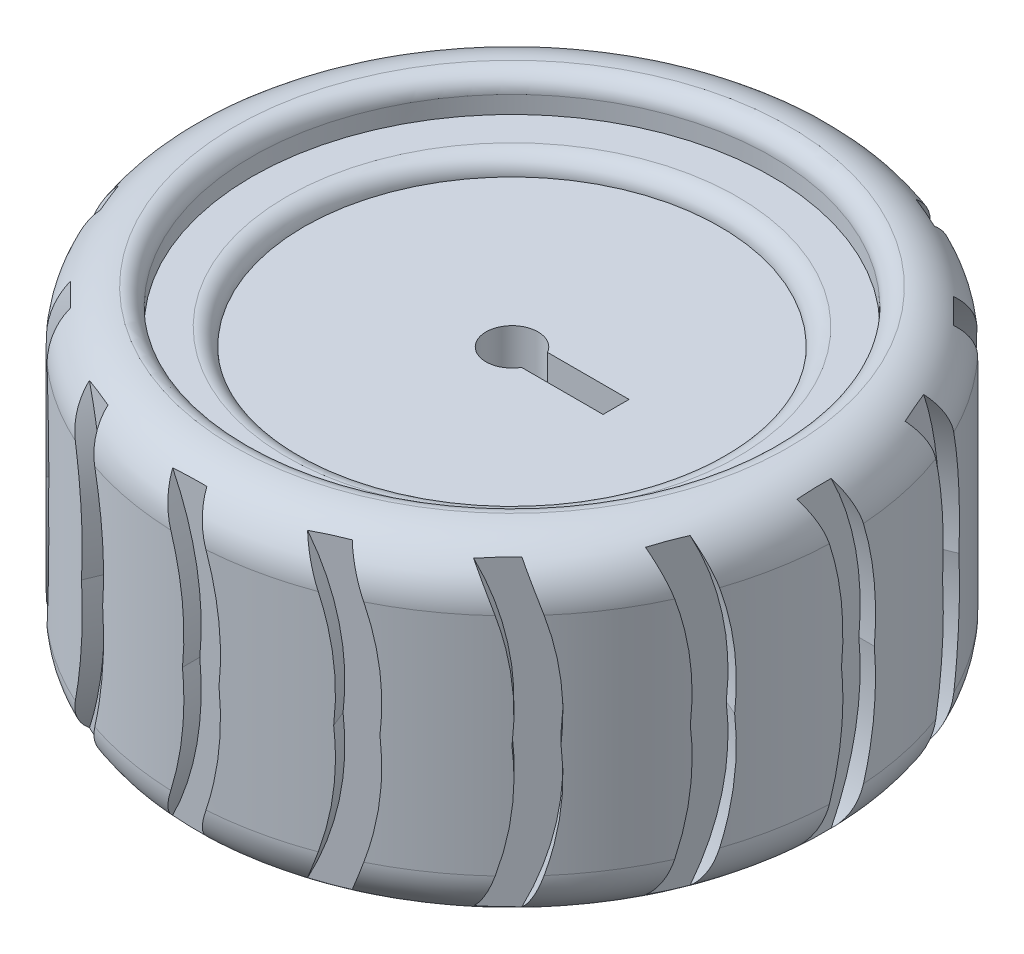
SolidWorks part; units mm, degrees
ref_plane "Front Plane" through (0, 0, 0) normal (0, 0, 1) x (1, 0, 0)
ref_plane "Top Plane" through (0, 0, 0) normal (0, 1, 0) x (1, 0, 0)
ref_plane "Right Plane" through (0, 0, 0) normal (1, 0, 0) x (0, 0, -1)
sketch "草图1" plane through (0, 0, 0) normal (0, 0, 1) x (1, 0, 0)
  line L0 (-688.0523, 0) -> (33714.563, 0) construction
  line L1 (0, -688.0523) -> (0, -10) construction
  line L3 (13, -7.5) -> (15, -7.5)
  line L4 (15, -7.5) -> (15, 7.5)
  line L5 (15, 7.5) -> (12, 7.5)
  line L6 (13, -7.5) -> (13, -2.5)
  line L7 (13, -2.5) -> (12, -2.5)
  line L8 (0, 6.5) -> (12, 6.5)
  line L9 (12, 6.5) -> (12, 7.5)
  line L10 (0, -2.5) -> (0, 33714.563) construction
  line L11 (0, 6.5) -> (0, -2.5)
  arc A0 (12, -2.5) -> (0, -2.5) centre (6, 5.8164) cw
  point P4 (15, 0)
  dimension "D1" = 15
  dimension "D3" = 2
  dimension "D4" = 5
  dimension "D6" = 1
revolve "旋转1" add sketch "草图1" angle 360 about L10
sketch "草图2" plane through (0, 6.5, 0) normal (0, 1, 0) x (1, 0, 0)
  line L0 (-1000, 0) -> (49000, 0) construction
  line L2 (1.299, -0.75) -> (6, -0.75)
  line L4 (1.299, 0.75) -> (6, 0.75)
  line L5 (6, -0.75) -> (6, 0.75)
  arc A0 (1.299, 0.75) -> (1.299, -0.75) centre (0, 0) ccw
  dimension "D1" = 3
  dimension "D2" = 1.5
extrude "切除-拉伸1" cut sketch "草图2" against normal through all both and the other way through all
sketch "草图3" plane through (0, -7.5, 0) normal (0, -1, 0) x (1, 0, 0)
  line L0 (12.9783, -0.75) -> (14.9812, -0.75)
  line L5 (12.7807, -2.3777) -> (14.7254, -2.857)
  line L6 (12.4217, -3.8341) -> (14.3664, -4.3135)
  line L7 (11.8403, -5.3672) -> (13.6138, -6.298)
  line L8 (11.1432, -6.6954) -> (12.9167, -7.6262)
  line L9 (12.9783, 0.75) -> (14.9812, 0.75)
  line L10 (10.2118, -8.0449) -> (11.711, -9.373)
  line L11 (9.2171, -9.1676) -> (10.7163, -10.4958)
  line L12 (7.9898, -10.2549) -> (9.1276, -11.9033)
  line L13 (6.7553, -11.107) -> (7.8931, -12.7554)
  line L14 (5.3034, -11.869) -> (6.0137, -13.7417)
  line L15 (3.9009, -12.4009) -> (4.6112, -14.2737)
  line L16 (2.3089, -12.7933) -> (2.5503, -14.7816)
  line L17 (0.8198, -12.9741) -> (1.0613, -14.9624)
  line L18 (-0.8198, -12.9741) -> (-1.0613, -14.9624)
  line L19 (-2.3089, -12.7933) -> (-2.5503, -14.7816)
  line L20 (-3.9009, -12.4009) -> (-4.6112, -14.2737)
  line L21 (-5.3034, -11.869) -> (-6.0137, -13.7417)
  line L22 (-6.7553, -11.107) -> (-7.8931, -12.7554)
  line L23 (-7.9898, -10.2549) -> (-9.1276, -11.9033)
  line L24 (-9.2171, -9.1676) -> (-10.7163, -10.4958)
  line L25 (-10.2118, -8.0449) -> (-11.711, -9.373)
  line L26 (-11.1432, -6.6954) -> (-12.9167, -7.6262)
  line L27 (-11.8403, -5.3672) -> (-13.6138, -6.298)
  line L28 (-12.4217, -3.8341) -> (-14.3664, -4.3135)
  line L29 (-12.7807, -2.3777) -> (-14.7254, -2.857)
  line L30 (-12.9783, -0.75) -> (-14.9812, -0.75)
  line L31 (-12.9783, 0.75) -> (-14.9812, 0.75)
  line L32 (-12.7807, 2.3777) -> (-14.7254, 2.857)
  line L33 (-12.4217, 3.8341) -> (-14.3664, 4.3135)
  line L34 (-11.8403, 5.3672) -> (-13.6138, 6.298)
  line L35 (-11.1432, 6.6954) -> (-12.9167, 7.6262)
  line L36 (-10.2118, 8.0449) -> (-11.711, 9.373)
  line L37 (-9.2171, 9.1676) -> (-10.7163, 10.4958)
  line L38 (-7.9898, 10.2549) -> (-9.1276, 11.9033)
  line L39 (-6.7553, 11.107) -> (-7.8931, 12.7554)
  line L40 (-5.3034, 11.869) -> (-6.0137, 13.7417)
  line L41 (-3.9009, 12.4009) -> (-4.6112, 14.2737)
  line L42 (-2.3089, 12.7933) -> (-2.5503, 14.7816)
  line L43 (-0.8198, 12.9741) -> (-1.0613, 14.9624)
  line L44 (0.8198, 12.9741) -> (1.0613, 14.9624)
  line L45 (2.3089, 12.7933) -> (2.5503, 14.7816)
  line L46 (3.9009, 12.4009) -> (4.6112, 14.2737)
  line L47 (5.3034, 11.869) -> (6.0137, 13.7417)
  line L48 (6.7553, 11.107) -> (7.8931, 12.7554)
  line L49 (7.9898, 10.2549) -> (9.1276, 11.9033)
  line L50 (9.2171, 9.1676) -> (10.7163, 10.4958)
  line L51 (10.2118, 8.0449) -> (11.711, 9.373)
  line L52 (11.1432, 6.6954) -> (12.9167, 7.6262)
  line L53 (11.8403, 5.3672) -> (13.6138, 6.298)
  line L54 (12.4217, 3.8341) -> (14.3664, 4.3135)
  line L55 (12.7807, 2.3777) -> (14.7254, 2.857)
  arc A4 (14.9812, -0.75) -> (14.9812, 0.75) centre (0, 0) ccw
  arc A5 (12.9783, -0.75) -> (12.9783, 0.75) centre (0, 0) ccw
  arc A6 (14.3664, -4.3135) -> (14.7254, -2.857) centre (0, 0) ccw
  arc A7 (12.4217, -3.8341) -> (12.7807, -2.3777) centre (0, 0) ccw
  arc A8 (12.9167, -7.6262) -> (13.6138, -6.298) centre (0, 0) ccw
  arc A9 (11.1432, -6.6954) -> (11.8403, -5.3672) centre (0, 0) ccw
  arc A10 (10.7163, -10.4958) -> (11.711, -9.373) centre (0, 0) ccw
  arc A11 (9.2171, -9.1676) -> (10.2118, -8.0449) centre (0, 0) ccw
  arc A12 (7.8931, -12.7554) -> (9.1276, -11.9033) centre (0, 0) ccw
  arc A13 (6.7553, -11.107) -> (7.9898, -10.2549) centre (0, 0) ccw
  arc A14 (4.6112, -14.2737) -> (6.0137, -13.7417) centre (0, 0) ccw
  arc A15 (3.9009, -12.4009) -> (5.3034, -11.869) centre (0, 0) ccw
  arc A16 (1.0613, -14.9624) -> (2.5503, -14.7816) centre (0, 0) ccw
  arc A17 (0.8198, -12.9741) -> (2.3089, -12.7933) centre (0, 0) ccw
  arc A18 (-2.5503, -14.7816) -> (-1.0613, -14.9624) centre (0, 0) ccw
  arc A19 (-2.3089, -12.7933) -> (-0.8198, -12.9741) centre (0, 0) ccw
  arc A20 (-6.0137, -13.7417) -> (-4.6112, -14.2737) centre (0, 0) ccw
  arc A21 (-5.3034, -11.869) -> (-3.9009, -12.4009) centre (0, 0) ccw
  arc A22 (-9.1276, -11.9033) -> (-7.8931, -12.7554) centre (0, 0) ccw
  arc A23 (-7.9898, -10.2549) -> (-6.7553, -11.107) centre (0, 0) ccw
  arc A24 (-11.711, -9.373) -> (-10.7163, -10.4958) centre (0, 0) ccw
  arc A25 (-10.2118, -8.0449) -> (-9.2171, -9.1676) centre (0, 0) ccw
  arc A26 (-13.6138, -6.298) -> (-12.9167, -7.6262) centre (0, 0) ccw
  arc A27 (-11.8403, -5.3672) -> (-11.1432, -6.6954) centre (0, 0) ccw
  arc A28 (-14.7254, -2.857) -> (-14.3664, -4.3135) centre (0, 0) ccw
  arc A29 (-12.7807, -2.3777) -> (-12.4217, -3.8341) centre (0, 0) ccw
  arc A30 (-14.9812, 0.75) -> (-14.9812, -0.75) centre (0, 0) ccw
  arc A31 (-12.9783, 0.75) -> (-12.9783, -0.75) centre (0, 0) ccw
  arc A32 (-14.3664, 4.3135) -> (-14.7254, 2.857) centre (0, 0) ccw
  arc A33 (-12.4217, 3.8341) -> (-12.7807, 2.3777) centre (0, 0) ccw
  arc A34 (-12.9167, 7.6262) -> (-13.6138, 6.298) centre (0, 0) ccw
  arc A35 (-11.1432, 6.6954) -> (-11.8403, 5.3672) centre (0, 0) ccw
  arc A36 (-10.7163, 10.4958) -> (-11.711, 9.373) centre (0, 0) ccw
  arc A37 (-9.2171, 9.1676) -> (-10.2118, 8.0449) centre (0, 0) ccw
  arc A38 (-7.8931, 12.7554) -> (-9.1276, 11.9033) centre (0, 0) ccw
  arc A39 (-6.7553, 11.107) -> (-7.9898, 10.2549) centre (0, 0) ccw
  arc A40 (-4.6112, 14.2737) -> (-6.0137, 13.7417) centre (0, 0) ccw
  arc A41 (-3.9009, 12.4009) -> (-5.3034, 11.869) centre (0, 0) ccw
  arc A42 (-1.0613, 14.9624) -> (-2.5503, 14.7816) centre (0, 0) ccw
  arc A43 (-0.8198, 12.9741) -> (-2.3089, 12.7933) centre (0, 0) ccw
  arc A44 (2.5503, 14.7816) -> (1.0613, 14.9624) centre (0, 0) ccw
  arc A45 (2.3089, 12.7933) -> (0.8198, 12.9741) centre (0, 0) ccw
  arc A46 (6.0137, 13.7417) -> (4.6112, 14.2737) centre (0, 0) ccw
  arc A47 (5.3034, 11.869) -> (3.9009, 12.4009) centre (0, 0) ccw
  arc A48 (9.1276, 11.9033) -> (7.8931, 12.7554) centre (0, 0) ccw
  arc A49 (7.9898, 10.2549) -> (6.7553, 11.107) centre (0, 0) ccw
  arc A50 (11.711, 9.373) -> (10.7163, 10.4958) centre (0, 0) ccw
  arc A51 (10.2118, 8.0449) -> (9.2171, 9.1676) centre (0, 0) ccw
  arc A52 (13.6138, 6.298) -> (12.9167, 7.6262) centre (0, 0) ccw
  arc A53 (11.8403, 5.3672) -> (11.1432, 6.6954) centre (0, 0) ccw
  arc A54 (14.7254, 2.857) -> (14.3664, 4.3135) centre (0, 0) ccw
  arc A55 (12.7807, 2.3777) -> (12.4217, 3.8341) centre (0, 0) ccw
  point P0 (0, 0)
  point P111 (0, 0)
  dimension "D1" = 26
extrude "切除-拉伸2" cut sketch "草图3" against normal blind 5
sketch "草图4" plane through (0, 0, 0) normal (0, 0, 1) x (1, 0, 0)
  line L0 (-1000, 0) -> (49000, 0) construction
  line L1 (0, -1000) -> (0, 49000) construction
  line L2 (15, 9.5) -> (15, -9.5)
  line L3 (15, -9.5) -> (19, -9.5)
  line L4 (15, 9.5) -> (19, 9.5)
  line L5 (19, 9.5) -> (19, -9.5)
  point P7 (15, 0)
  dimension "D1" = 19
  dimension "D2" = 15
  dimension "D3" = 19
revolve "旋转2" add sketch "草图4" angle 360 about L1
fillet "圆角1" radius 1 3 edges at (0, -9.5, -15) (0, 9.5, -15) (12, 7.5, 0)
fillet "圆角2" radius 3 2 edges at (0, -9.5, -19) (0, 9.5, -19)
ref_plane "基准面1" through (0, 0, -25) normal (0, 0, 1) x (1, 0, 0)
sketch "草图6" plane through (0, 0, -25) normal (0, 0, 1) x (1, 0, 0)
  line L0 (-1000, 0) -> (49000, 0) construction
  line L1 (0, -1000) -> (0, 49000) construction
  line L2 (0, 9.5) -> (2, 9.5)
  line L7 (2, -9.5) -> (0, -9.5)
  arc A0 (0, 9.5) -> (-2, 0) centre (14.0582, 1.5799) ccw
  arc A1 (2, 9.5) -> (0, 0) centre (15.9512, 1.6024) ccw
  arc A2 (2, -9.5) -> (0, 0) centre (15.9512, -1.6024) cw
  arc A3 (0, -9.5) -> (-2, 0) centre (14.0582, -1.5799) cw
  dimension "D1" = 2
  dimension "D2" = 2
extrude "切除-拉伸7" cut sketch "草图6" along normal blind 7
pattern_circular "阵列(圆周)3" count 16 over 360 about axis through (0, 9.5, 0) along (0, -1, 0) of "切除-拉伸7"
equation "\"21。5\"=23.1901"
equation "\"1。5\"=2"
